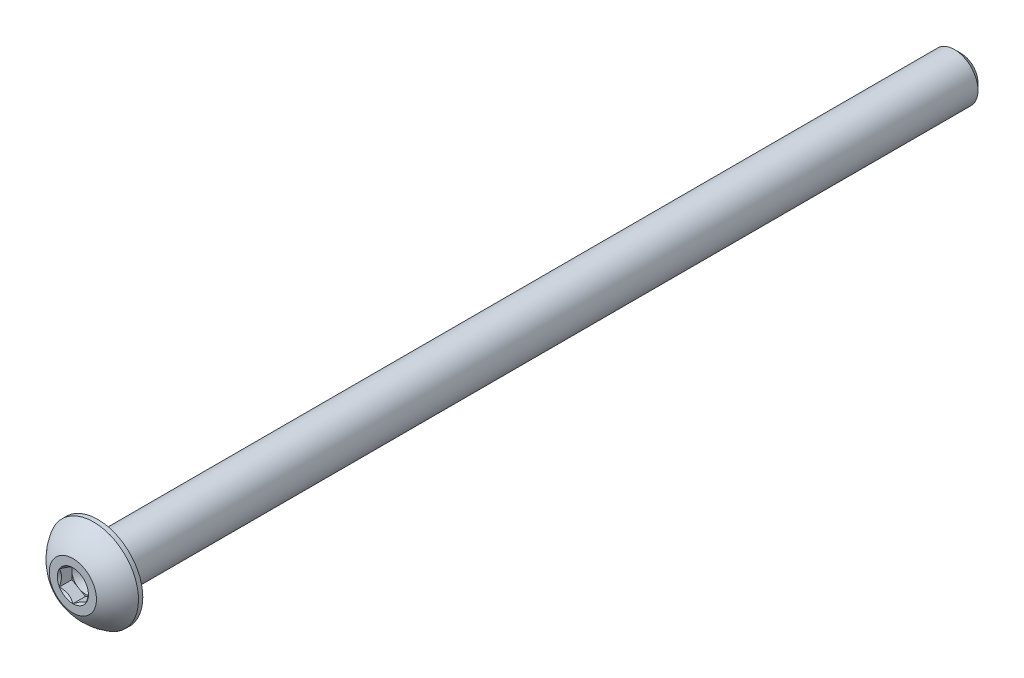
SolidWorks part; units mm, degrees
ref_plane "Front" through (0, 0, 0) normal (0, 0, 1) x (1, 0, 0)
ref_plane "Top" through (0, 0, 0) normal (0, 1, 0) x (1, 0, 0)
ref_plane "Right" through (0, 0, 0) normal (1, 0, 0) x (0, 0, -1)
sketch "Sketch1" plane through (0, 0, 0) normal (1, 0, 0) x (0, 0, -1)
  line L0 (0, 0) -> (-2.2098, 0) construction
  line L1 (0, 0) -> (76.2, 0)
  line L2 (0, 0) -> (0, 2.0828)
  line L3 (0, 2.0828) -> (76.2, 2.0828)
  line L4 (76.2, 0) -> (76.2, 2.0828)
  line L5 (0, -2.0828) -> (76.2, -2.0828) construction
  dimension "D1" = 76.2
  dimension "Thread Dia" = 4.1656
  dimension "Length" = 76.2
  dimension "Head Height" = 2.2098
revolve "Revolve1" add sketch "Sketch1" angle 360 about L0
ref_plane "Plane1" through (0, 0, 2.2098) normal (0, 0, 1) x (1, 0, 0)
chamfer "Chamfer1" distance 0.5953 angle 45 1 edges at (0, 2.0828, -76.2)
sketch "Sketch10" plane through (0, 0, 0) normal (1, 0, 0) x (0, 0, -1)
  line L0 (76.2, 2.0828) -> (76.8945, 2.0828)
  line L1 (76.8945, 2.0828) -> (76.5969, 1.5672)
  line L2 (76.5969, 1.5672) -> (76.4977, 1.5672)
  line L3 (76.4977, 1.5672) -> (76.2, 2.0828)
  line L4 (76.3488, 1.825) -> (76.7457, 1.825) construction
  dimension "D1" = 60
  dimension "D2" = 0.0992
  dimension "D3" = 0.3969
sketch "Sketch11" plane through (0, 0, -76.2) normal (0, 0, -1) x (-1, 0, 0)
  circle A1 centre (0, 0) radius 1.4875
  circle A2 centre (0, 0) radius 1.4875
  dimension "D1" = 0
curve "Helix/Spiral1" [suppressed] pitch 0.7937 height 79.375 turns 100
sweep "Cut-Sweep1" [suppressed] cut profiles "Sketch10" path "Helix/Spiral1"
sketch "Sketch4" plane through (0, 0, 0) normal (0, 0, 1) x (1, 0, 0)
  circle A0 centre (0, 0) radius 3.9624
  dimension "Head Dia" = 7.9248
extrude "Extrude1" add sketch "Sketch4" along normal up to surface (2.2098 mm away) up to plane "Plane1"
sketch "Sketch9" plane through (0, 0, 0) normal (1, 0, 0) x (0, 0, -1)
  line L0 (0, 3.9624) -> (-0.381, 3.9624)
  line L1 (0, 3.9624) -> (0, 4.3434)
  line L2 (0, 4.3434) -> (-2.5908, 4.3434)
  line L3 (0, 0) -> (-2.2098, 0) construction
  line L4 (-2.5908, 4.3434) -> (-2.5908, 2.0828)
  line L5 (-2.5908, 2.0828) -> (-2.2098, 2.0828)
  line L6 (0, 0) -> (0, 2.0828) construction
  line L10 (0, 3.9624) -> (-2.2098, 3.9624) construction
  line L11 (0, 2.0828) -> (76.2, 2.0828) construction
  line L12 (-2.2098, 3.9624) -> (-2.2098, -3.9624) construction
  arc A0 (-2.2098, 2.0828) -> (-0.381, 3.9624) centre (1.8112, 0) cw
  dimension "Side Head Height" = 0.381
revolve "Cut-Revolve3" cut sketch "Sketch9" angle 360 about L3
sketch "Sketch6" plane through (0, 0, 2.2098) normal (0, 0, 1) x (1, 0, 0)
  line L1 (0, -1.3748) -> (1.1906, -0.6874)
  line L2 (1.1906, -0.6874) -> (1.1906, 0.6874)
  line L3 (1.1906, 0.6874) -> (0, 1.3748)
  line L4 (0, 1.3748) -> (-1.1906, 0.6874)
  line L5 (-1.1906, 0.6874) -> (-1.1906, -0.6874)
  line L6 (-1.1906, -0.6874) -> (0, -1.3748)
  circle A0 centre (0, 0) radius 1.1906 construction
  dimension "Hex" = 2.3813
extrude "Cut-Extrude1" cut sketch "Sketch6" against normal blind 1.1049
sketch "Sketch7" plane through (0, 0, 2.2098) normal (0, 0, 1) x (1, 0, 0)
  circle A0 centre (0, 0) radius 1.3748
extrude "Cut-Extrude4" cut sketch "Sketch7" against normal blind 1.1049 draft 45
sketch "Sketch8" plane through (0, 0, 1.1049) normal (0, 0, 1) x (1, 0, 0)
  circle A0 centre (0, 0) radius 1.1906 construction
  circle A1 centre (0, 0) radius 1.1906
extrude "Cut-Extrude5" cut sketch "Sketch8" against normal blind 0.3683 draft 60
sketch "Sketch12" [suppressed] plane through (0, 0, 0) normal (1, 0, 0) x (0, 0, -1)
  line L1 (0, -2.0828) -> (76.2, -2.0828) construction
  spline S2 degree 2 poles (75.6047, 0.019) (75.5523, 0.8706) (75.5055, 1.4728) (75.4393, 2.3231) (75.3732, 2.0118) (75.307, 1.7006) (75.2409, 0.5391) (75.1747, -0.6225) (75.1086, -1.4728) (75.0424, -2.3231) (74.9763, -2.0118) (74.9102, -1.7006) (74.844, -0.5391) (74.7779, 0.6225) (74.7117, 1.4728) (74.6456, 2.3231) (74.5794, 2.0118) (74.5133, 1.7006) (74.4471, 0.5391) (74.381, -0.6225) (74.3148, -1.4728) (74.2487, -2.3231) (74.1826, -2.0118) (74.1164, -1.7006) (74.0503, -0.5391) (73.9841, 0.6225) (73.918, 1.4728) (73.8518, 2.3231) (73.7857, 2.0118) (73.7195, 1.7006) (73.6534, 0.5391) (73.5872, -0.6225) (73.5211, -1.4728) (73.4549, -2.3231) (73.3888, -2.0118) (73.3227, -1.7006) (73.2565, -0.5391) (73.1904, 0.6225) (73.1242, 1.4728) (73.0581, 2.3231) (72.9919, 2.0118) (72.9258, 1.7006) (72.8596, 0.5391) (72.7935, -0.6225) (72.7273, -1.4728) (72.6612, -2.3231) (72.5951, -2.0118) (72.5289, -1.7006) (72.4628, -0.5391) (72.3966, 0.6225) (72.3305, 1.4728) (72.2643, 2.3231) (72.1982, 2.0118) (72.132, 1.7006) (72.0659, 0.5391) (71.9997, -0.6225) (71.9336, -1.4728) (71.8674, -2.3231) (71.8013, -2.0118) (71.7352, -1.7006) (71.669, -0.5391) (71.6029, 0.6225) (71.5367, 1.4728) (71.4706, 2.3231) (71.4044, 2.0118) (71.3383, 1.7006) (71.2721, 0.5391) (71.206, -0.6225) (71.1398, -1.4728) (71.0737, -2.3231) (71.0076, -2.0118) (70.9414, -1.7006) (70.8753, -0.5391) (70.8091, 0.6225) (70.743, 1.4728) (70.6768, 2.3231) (70.6107, 2.0118) (70.5445, 1.7006) (70.4784, 0.5391) (70.4122, -0.6225) (70.3461, -1.4728) (70.2799, -2.3231) (70.2138, -2.0118) (70.1477, -1.7006) (70.0815, -0.5391) (70.0154, 0.6225) (69.9492, 1.4728) (69.8831, 2.3231) (69.8169, 2.0118) (69.7508, 1.7006) (69.6846, 0.5391) (69.6185, -0.6225) (69.5523, -1.4728) (69.4862, -2.3231) (69.4201, -2.0118) (69.3539, -1.7006) (69.2878, -0.5391) (69.2216, 0.6225) (69.1555, 1.4728) (69.0893, 2.3231) (69.0232, 2.0118) (68.957, 1.7006) (68.8909, 0.5391) (68.8247, -0.6225) (68.7586, -1.4728) (68.6924, -2.3231) (68.6263, -2.0118) (68.5602, -1.7006) (68.494, -0.5391) (68.4279, 0.6225) (68.3617, 1.4728) (68.2956, 2.3231) (68.2294, 2.0118) (68.1633, 1.7006) (68.0971, 0.5391) (68.031, -0.6225) (67.9648, -1.4728) (67.8987, -2.3231) (67.8326, -2.0118) (67.7664, -1.7006) (67.7003, -0.5391) (67.6341, 0.6225) (67.568, 1.4728) (67.5018, 2.3231) (67.4357, 2.0118) (67.3695, 1.7006) (67.3034, 0.5391) (67.2372, -0.6225) (67.1711, -1.4728) (67.1049, -2.3231) (67.0388, -2.0118) (66.9727, -1.7006) (66.9065, -0.5391) (66.8404, 0.6225) (66.7742, 1.4728) (66.7081, 2.3231) (66.6419, 2.0118) (66.5758, 1.7006) (66.5096, 0.5391) (66.4435, -0.6225) (66.3773, -1.4728) (66.3112, -2.3231) (66.2451, -2.0118) (66.1789, -1.7006) (66.1128, -0.5391) (66.0466, 0.6225) (65.9805, 1.4728) (65.9143, 2.3231) (65.8482, 2.0118) (65.782, 1.7006) (65.7159, 0.5391) (65.6497, -0.6225) (65.5836, -1.4728) (65.5174, -2.3231) (65.4513, -2.0118) (65.3852, -1.7006) (65.319, -0.5391) (65.2529, 0.6225) (65.1867, 1.4728) (65.1206, 2.3231) (65.0544, 2.0118) (64.9883, 1.7006) (64.9221, 0.5391) (64.856, -0.6225) (64.7898, -1.4728) (64.7237, -2.3231) (64.6576, -2.0118) (64.5914, -1.7006) (64.5253, -0.5391) (64.4591, 0.6225) (64.393, 1.4728) (64.3268, 2.3231) (64.2607, 2.0118) (64.1945, 1.7006) (64.1284, 0.5391) (64.0622, -0.6225) (63.9961, -1.4728) (63.9299, -2.3231) (63.8638, -2.0118) (63.7977, -1.7006) (63.7315, -0.5391) (63.6654, 0.6225) (63.5992, 1.4728) (63.5331, 2.3231) (63.4669, 2.0118) (63.4008, 1.7006) (63.3346, 0.5391) (63.2685, -0.6225) (63.2023, -1.4728) (63.1362, -2.3231) (63.0701, -2.0118) (63.0039, -1.7006) (62.9378, -0.5391) (62.8716, 0.6225) (62.8055, 1.4728) (62.7393, 2.3231) (62.6732, 2.0118) (62.607, 1.7006) (62.5409, 0.5391) (62.4747, -0.6225) (62.4086, -1.4728) (62.3424, -2.3231) (62.2763, -2.0118) (62.2102, -1.7006) (62.144, -0.5391) (62.0779, 0.6225) (62.0117, 1.4728) (61.9456, 2.3231) (61.8794, 2.0118) (61.8133, 1.7006) (61.7471, 0.5391) (61.681, -0.6225) (61.6148, -1.4728) (61.5487, -2.3231) (61.4826, -2.0118) (61.4164, -1.7006) (61.3503, -0.5391) (61.2841, 0.6225) (61.218, 1.4728) (61.1518, 2.3231) (61.0857, 2.0118) (61.0195, 1.7006) (60.9534, 0.5391) (60.8872, -0.6225) (60.8211, -1.4728) (60.7549, -2.3231) (60.6888, -2.0118) (60.6227, -1.7006) (60.5565, -0.5391) (60.4904, 0.6225) (60.4242, 1.4728) (60.3581, 2.3231) (60.2919, 2.0118) (60.2258, 1.7006) (60.1596, 0.5391) (60.0935, -0.6225) (60.0273, -1.4728) (59.9612, -2.3231) (59.8951, -2.0118) (59.8289, -1.7006) (59.7628, -0.5391) (59.6966, 0.6225) (59.6305, 1.4728) (59.5643, 2.3231) (59.4982, 2.0118) (59.432, 1.7006) (59.3659, 0.5391) (59.2997, -0.6225) (59.2336, -1.4728) (59.1674, -2.3231) (59.1013, -2.0118) (59.0352, -1.7006) (58.969, -0.5391) (58.9029, 0.6225) (58.8367, 1.4728) (58.7706, 2.3231) (58.7044, 2.0118) (58.6383, 1.7006) (58.5721, 0.5391) (58.506, -0.6225) (58.4398, -1.4728) (58.3737, -2.3231) (58.3076, -2.0118) (58.2414, -1.7006) (58.1753, -0.5391) (58.1091, 0.6225) (58.043, 1.4728) (57.9768, 2.3231) (57.9107, 2.0118) (57.8445, 1.7006) (57.7784, 0.5391) (57.7122, -0.6225) (57.6461, -1.4728) (57.5799, -2.3231) (57.5138, -2.0118) (57.4477, -1.7006) (57.3815, -0.5391) (57.3154, 0.6225) (57.2492, 1.4728) (57.1831, 2.3231) (57.1169, 2.0118) (57.0508, 1.7006) (56.9846, 0.5391) (56.9185, -0.6225) (56.8523, -1.4728) (56.7862, -2.3231) (56.7201, -2.0118) (56.6539, -1.7006) (56.5878, -0.5391) (56.5216, 0.6225) (56.4555, 1.4728) (56.3893, 2.3231) (56.3232, 2.0118) (56.257, 1.7006) (56.1909, 0.5391) (56.1247, -0.6225) (56.0586, -1.4728) (55.9924, -2.3231) (55.9263, -2.0118) (55.8602, -1.7006) (55.794, -0.5391) (55.7279, 0.6225) (55.6617, 1.4728) (55.5956, 2.3231) (55.5294, 2.0118) (55.4633, 1.7006) (55.3971, 0.5391) (55.331, -0.6225) (55.2648, -1.4728) (55.1987, -2.3231) (55.1326, -2.0118) (55.0664, -1.7006) (55.0003, -0.5391) (54.9341, 0.6225) (54.868, 1.4728) (54.8018, 2.3231) (54.7357, 2.0118) (54.6695, 1.7006) (54.6034, 0.5391) (54.5372, -0.6225) (54.4711, -1.4728) (54.4049, -2.3231) (54.3388, -2.0118) (54.2727, -1.7006) (54.2065, -0.5391) (54.1404, 0.6225) (54.0742, 1.4728) (54.0081, 2.3231) (53.9419, 2.0118) (53.8758, 1.7006) (53.8096, 0.5391) (53.7435, -0.6225) (53.6773, -1.4728) (53.6112, -2.3231) (53.5451, -2.0118) (53.4789, -1.7006) (53.4128, -0.5391) (53.3466, 0.6225) (53.2805, 1.4728) (53.2143, 2.3231) (53.1482, 2.0118) (53.082, 1.7006) (53.0159, 0.5391) (52.9497, -0.6225) (52.8836, -1.4728) (52.8174, -2.3231) (52.7513, -2.0118) (52.6852, -1.7006) (52.619, -0.5391) (52.5529, 0.6225) (52.4867, 1.4728) (52.4206, 2.3231) (52.3544, 2.0118) (52.2883, 1.7006) (52.2221, 0.5391) (52.156, -0.6225) (52.0898, -1.4728) (52.0237, -2.3231) (51.9576, -2.0118) (51.8914, -1.7006) (51.8253, -0.5391) (51.7591, 0.6225) (51.693, 1.4728) (51.6268, 2.3231) (51.5607, 2.0118) (51.4945, 1.7006) (51.4284, 0.5391) (51.3622, -0.6225) (51.2961, -1.4728) (51.2299, -2.3231) (51.1638, -2.0118) (51.0977, -1.7006) (51.0315, -0.5391) (50.9654, 0.6225) (50.8992, 1.4728) (50.8331, 2.3231) (50.7669, 2.0118) (50.7008, 1.7006) (50.6346, 0.5391) (50.5685, -0.6225) (50.5023, -1.4728) (50.4362, -2.3231) (50.3701, -2.0118) (50.3039, -1.7006) (50.2378, -0.5391) (50.1716, 0.6225) (50.1055, 1.4728) (50.0393, 2.3231) (49.9732, 2.0118) (49.907, 1.7006) (49.8409, 0.5391) (49.7747, -0.6225) (49.7086, -1.4728) (49.6424, -2.3231) (49.5763, -2.0118) (49.5102, -1.7006) (49.444, -0.5391) (49.3779, 0.6225) (49.3117, 1.4728) (49.2456, 2.3231) (49.1794, 2.0118) (49.1133, 1.7006) (49.0471, 0.5391) (48.981, -0.6225) (48.9148, -1.4728) (48.8487, -2.3231) (48.7826, -2.0118) (48.7164, -1.7006) (48.6503, -0.5391) (48.5841, 0.6225) (48.518, 1.4728) (48.4518, 2.3231) (48.3857, 2.0118) (48.3195, 1.7006) (48.2534, 0.5391) (48.1872, -0.6225) (48.1211, -1.4728) (48.0549, -2.3231) (47.9888, -2.0118) (47.9227, -1.7006) (47.8565, -0.5391) (47.7904, 0.6225) (47.7242, 1.4728) (47.6581, 2.3231) (47.5919, 2.0118) (47.5258, 1.7006) (47.4596, 0.5391) (47.3935, -0.6225) (47.3273, -1.4728) (47.2612, -2.3231) (47.1951, -2.0118) (47.1289, -1.7006) (47.0628, -0.5391) (46.9966, 0.6225) (46.9305, 1.4728) (46.8643, 2.3231) (46.7982, 2.0118) (46.732, 1.7006) (46.6659, 0.5391) (46.5997, -0.6225) (46.5336, -1.4728) (46.4674, -2.3231) (46.4013, -2.0118) (46.3352, -1.7006) (46.269, -0.5391) (46.2029, 0.6225) (46.1367, 1.4728) (46.0706, 2.3231) (46.0044, 2.0118) (45.9383, 1.7006) (45.8721, 0.5391) (45.806, -0.6225) (45.7398, -1.4728) (45.6737, -2.3231) (45.6076, -2.0118) (45.5414, -1.7006) (45.4753, -0.5391) (45.4091, 0.6225) (45.343, 1.4728) (45.2768, 2.3231) (45.2107, 2.0118) (45.1445, 1.7006) (45.0784, 0.5391) (45.0122, -0.6225) (44.9461, -1.4728) (44.8799, -2.3231) (44.8138, -2.0118) (44.7477, -1.7006) (44.6815, -0.5391) (44.6154, 0.6225) (44.5492, 1.4728) (44.4831, 2.3231) (44.4169, 2.0118) (44.3508, 1.7006) (44.2846, 0.5391) (44.2185, -0.6225) (44.1523, -1.4728) (44.0862, -2.3231) (44.0201, -2.0118) (43.9539, -1.7006) (43.8878, -0.5391) (43.8216, 0.6225) (43.7555, 1.4728) (43.6893, 2.3231) (43.6232, 2.0118) (43.557, 1.7006) (43.4909, 0.5391) (43.4247, -0.6225) (43.3586, -1.4728) (43.2924, -2.3231) (43.2263, -2.0118) (43.1602, -1.7006) (43.094, -0.5391) (43.0279, 0.6225) (42.9617, 1.4728) (42.8956, 2.3231) (42.8294, 2.0118) (42.7633, 1.7006) (42.6971, 0.5391) (42.631, -0.6225) (42.5648, -1.4728) (42.4987, -2.3231) (42.4326, -2.0118) (42.3664, -1.7006) (42.3003, -0.5391) (42.2341, 0.6225) (42.168, 1.4728) (42.1018, 2.3231) (42.0357, 2.0118) (41.9695, 1.7006) (41.9034, 0.5391) (41.8372, -0.6225) (41.7711, -1.4728) (41.7049, -2.3231) (41.6388, -2.0118) (41.5727, -1.7006) (41.5065, -0.5391) (41.4404, 0.6225) (41.3742, 1.4728) (41.3081, 2.3231) (41.2419, 2.0118) (41.1758, 1.7006) (41.1096, 0.5391) (41.0435, -0.6225) (40.9773, -1.4728) (40.9112, -2.3231) (40.8451, -2.0118) (40.7789, -1.7006) (40.7128, -0.5391) (40.6466, 0.6225) (40.5805, 1.4728) (40.5143, 2.3231) (40.4482, 2.0118) (40.382, 1.7006) (40.3159, 0.5391) (40.2497, -0.6225) (40.1836, -1.4728) (40.1174, -2.3231) (40.0513, -2.0118) (39.9852, -1.7006) (39.919, -0.5391) (39.8529, 0.6225) (39.7867, 1.4728) (39.7206, 2.3231) (39.6544, 2.0118) (39.5883, 1.7006) (39.5221, 0.5391) (39.456, -0.6225) (39.3898, -1.4728) (39.3237, -2.3231) (39.2576, -2.0118) (39.1914, -1.7006) (39.1253, -0.5391) (39.0591, 0.6225) (38.993, 1.4728) (38.9268, 2.3231) (38.8607, 2.0118) (38.7945, 1.7006) (38.7284, 0.5391) (38.6622, -0.6225) (38.5961, -1.4728) (38.5299, -2.3231) (38.4638, -2.0118) (38.3977, -1.7006) (38.3315, -0.5391) (38.2654, 0.6225) (38.1992, 1.4728) (38.1331, 2.3231) (38.0669, 2.0118) (38.0008, 1.7006) (37.9346, 0.5391) (37.8685, -0.6225) (37.8023, -1.4728) (37.7362, -2.3231) (37.6701, -2.0118) (37.6039, -1.7006) (37.5378, -0.5391) (37.4716, 0.6225) (37.4055, 1.4728) (37.3393, 2.3231) (37.2732, 2.0118) (37.207, 1.7006) (37.1409, 0.5391) (37.0747, -0.6225) (37.0086, -1.4728) (36.9424, -2.3231) (36.8763, -2.0118) (36.8102, -1.7006) (36.744, -0.5391) (36.6779, 0.6225) (36.6117, 1.4728) (36.5456, 2.3231) (36.4794, 2.0118) (36.4133, 1.7006) (36.3471, 0.5391) (36.281, -0.6225) (36.2148, -1.4728) (36.1487, -2.3231) (36.0826, -2.0118) (36.0164, -1.7006) (35.9503, -0.5391) (35.8841, 0.6225) (35.818, 1.4728) (35.7518, 2.3231) (35.6857, 2.0118) (35.6195, 1.7006) (35.5534, 0.5391) (35.4872, -0.6225) (35.4211, -1.4728) (35.3549, -2.3231) (35.2888, -2.0118) (35.2227, -1.7006) (35.1565, -0.5391) (35.0904, 0.6225) (35.0242, 1.4728) (34.9581, 2.3231) (34.8919, 2.0118) (34.8258, 1.7006) (34.7596, 0.5391) (34.6935, -0.6225) (34.6273, -1.4728) (34.5612, -2.3231) (34.4951, -2.0118) (34.4289, -1.7006) (34.3628, -0.5391) (34.2966, 0.6225) (34.2305, 1.4728) (34.1643, 2.3231) (34.0982, 2.0118) (34.032, 1.7006) (33.9659, 0.5391) (33.8997, -0.6225) (33.8336, -1.4728) (33.7674, -2.3231) (33.7013, -2.0118) (33.6352, -1.7006) (33.569, -0.5391) (33.5029, 0.6225) (33.4367, 1.4728) (33.3706, 2.3231) (33.3044, 2.0118) (33.2383, 1.7006) (33.1721, 0.5391) (33.106, -0.6225) (33.0398, -1.4728) (32.9737, -2.3231) (32.9076, -2.0118) (32.8414, -1.7006) (32.7753, -0.5391) (32.7091, 0.6225) (32.643, 1.4728) (32.5768, 2.3231) (32.5107, 2.0118) (32.4445, 1.7006) (32.3784, 0.5391) (32.3122, -0.6225) (32.2461, -1.4728) (32.1799, -2.3231) (32.1138, -2.0118) (32.0477, -1.7006) (31.9815, -0.5391) (31.9154, 0.6225) (31.8492, 1.4728) (31.7831, 2.3231) (31.7169, 2.0118) (31.6508, 1.7006) (31.5846, 0.5391) (31.5185, -0.6225) (31.4523, -1.4728) (31.3862, -2.3231) (31.3201, -2.0118) (31.2539, -1.7006) (31.1878, -0.5391) (31.1216, 0.6225) (31.0555, 1.4728) (30.9893, 2.3231) (30.9232, 2.0118) (30.857, 1.7006) (30.7909, 0.5391) (30.7247, -0.6225) (30.6586, -1.4728) (30.5924, -2.3231) (30.5263, -2.0118) (30.4602, -1.7006) (30.394, -0.5391) (30.3279, 0.6225) (30.2617, 1.4728) (30.1956, 2.3231) (30.1294, 2.0118) (30.0633, 1.7006) (29.9971, 0.5391) (29.931, -0.6225) (29.8648, -1.4728) (29.7987, -2.3231) (29.7326, -2.0118) (29.6664, -1.7006) (29.6003, -0.5391) (29.5341, 0.6225) (29.468, 1.4728) (29.4018, 2.3231) (29.3357, 2.0118) (29.2695, 1.7006) (29.2034, 0.5391) (29.1372, -0.6225) (29.0711, -1.4728) (29.0049, -2.3231) (28.9388, -2.0118) (28.8727, -1.7006) (28.8065, -0.5391) (28.7404, 0.6225) (28.6742, 1.4728) (28.6081, 2.3231) (28.5419, 2.0118) (28.4758, 1.7006) (28.4096, 0.5391) (28.3435, -0.6225) (28.2773, -1.4728) (28.2112, -2.3231) (28.1451, -2.0118) (28.0789, -1.7006) (28.0128, -0.5391) (27.9466, 0.6225) (27.8805, 1.4728) (27.8143, 2.3231) (27.7482, 2.0118) (27.682, 1.7006) (27.6159, 0.5391) (27.5497, -0.6225) (27.4836, -1.4728) (27.4174, -2.3231) (27.3513, -2.0118) (27.2852, -1.7006) (27.219, -0.5391) (27.1529, 0.6225) (27.0867, 1.4728) (27.0206, 2.3231) (26.9544, 2.0118) (26.8883, 1.7006) (26.8221, 0.5391) (26.756, -0.6225) (26.6898, -1.4728) (26.6237, -2.3231) (26.5576, -2.0118) (26.4914, -1.7006) (26.4253, -0.5391) (26.3591, 0.6225) (26.293, 1.4728) (26.2268, 2.3231) (26.1607, 2.0118) (26.0945, 1.7006) (26.0284, 0.5391) (25.9622, -0.6225) (25.8961, -1.4728) (25.8299, -2.3231) (25.7638, -2.0118) (25.6977, -1.7006) (25.6315, -0.5391) (25.5654, 0.6225) (25.4992, 1.4728) (25.4331, 2.3231) (25.3669, 2.0118) (25.3008, 1.7006) (25.2346, 0.5391) (25.1685, -0.6225) (25.1023, -1.4728) (25.0362, -2.3231) (24.9701, -2.0118) (24.9039, -1.7006) (24.8378, -0.5391) (24.7716, 0.6225) (24.7055, 1.4728) (24.6393, 2.3231) (24.5732, 2.0118) (24.507, 1.7006) (24.4409, 0.5391) (24.3747, -0.6225) (24.3086, -1.4728) (24.2424, -2.3231) (24.1763, -2.0118) (24.1102, -1.7006) (24.044, -0.5391) (23.9779, 0.6225) (23.9117, 1.4728) (23.8456, 2.3231) (23.7794, 2.0118) (23.7133, 1.7006) (23.6471, 0.5391) (23.581, -0.6225) (23.5148, -1.4728) (23.4487, -2.3231) (23.3826, -2.0118) (23.3164, -1.7006) (23.2503, -0.5391) (23.1841, 0.6225) (23.118, 1.4728) (23.0518, 2.3231) (22.9857, 2.0118) (22.9195, 1.7006) (22.8534, 0.5391) (22.7872, -0.6225) (22.7211, -1.4728) (22.6549, -2.3231) (22.5888, -2.0118) (22.5227, -1.7006) (22.4565, -0.5391) (22.3904, 0.6225) (22.3242, 1.4728) (22.2581, 2.3231) (22.1919, 2.0118) (22.1258, 1.7006) (22.0596, 0.5391) (21.9935, -0.6225) (21.9273, -1.4728) (21.8612, -2.3231) (21.7951, -2.0118) (21.7289, -1.7006) (21.6628, -0.5391) (21.5966, 0.6225) (21.5305, 1.4728) (21.4643, 2.3231) (21.3982, 2.0118) (21.332, 1.7006) (21.2659, 0.5391) (21.1997, -0.6225) (21.1336, -1.4728) (21.0674, -2.3231) (21.0013, -2.0118) (20.9352, -1.7006) (20.869, -0.5391) (20.8029, 0.6225) (20.7367, 1.4728) (20.6706, 2.3231) (20.6044, 2.0118) (20.5383, 1.7006) (20.4721, 0.5391) (20.406, -0.6225) (20.3398, -1.4728) (20.2737, -2.3231) (20.2076, -2.0118) (20.1414, -1.7006) (20.0753, -0.5391) (20.0091, 0.6225) (19.943, 1.4728) (19.8768, 2.3231) (19.8107, 2.0118) (19.7445, 1.7006) (19.6784, 0.5391) (19.6122, -0.6225) (19.5461, -1.4728) (19.4799, -2.3231) (19.4138, -2.0118) (19.3477, -1.7006) (19.2815, -0.5391) (19.2154, 0.6225) (19.1492, 1.4728) (19.0831, 2.3231) (19.0169, 2.0118) (18.9508, 1.7006) (18.8846, 0.5391) (18.8185, -0.6225) (18.7523, -1.4728) (18.6862, -2.3231) (18.6201, -2.0118) (18.5539, -1.7006) (18.4878, -0.5391) (18.4216, 0.6225) (18.3555, 1.4728) (18.2893, 2.3231) (18.2232, 2.0118) (18.157, 1.7006) (18.0909, 0.5391) (18.0247, -0.6225) (17.9586, -1.4728) (17.8924, -2.3231) (17.8263, -2.0118) (17.7602, -1.7006) (17.694, -0.5391) (17.6279, 0.6225) (17.5617, 1.4728) (17.4956, 2.3231) (17.4294, 2.0118) (17.3633, 1.7006) (17.2971, 0.5391) (17.231, -0.6225) (17.1648, -1.4728) (17.0987, -2.3231) (17.0326, -2.0118) (16.9664, -1.7006) (16.9003, -0.5391) (16.8341, 0.6225) (16.768, 1.4728) (16.7018, 2.3231) (16.6357, 2.0118) (16.5695, 1.7006) (16.5034, 0.5391) (16.4372, -0.6225) (16.3711, -1.4728) (16.3049, -2.3231) (16.2388, -2.0118) (16.1727, -1.7006) (16.1065, -0.5391) (16.0404, 0.6225) (15.9742, 1.4728) (15.9081, 2.3231) (15.8419, 2.0118) (15.7758, 1.7006) (15.7096, 0.5391) (15.6435, -0.6225) (15.5773, -1.4728) (15.5112, -2.3231) (15.4451, -2.0118) (15.3789, -1.7006) (15.3128, -0.5391) (15.2466, 0.6225) (15.1805, 1.4728) (15.1143, 2.3231) (15.0482, 2.0118) (14.982, 1.7006) (14.9159, 0.5391) (14.8497, -0.6225) (14.7836, -1.4728) (14.7174, -2.3231) (14.6513, -2.0118) (14.5852, -1.7006) (14.519, -0.5391) (14.4529, 0.6225) (14.3867, 1.4728) (14.3206, 2.3231) (14.2544, 2.0118) (14.1883, 1.7006) (14.1221, 0.5391) (14.056, -0.6225) (13.9898, -1.4728) (13.9237, -2.3231) (13.8576, -2.0118) (13.7914, -1.7006) (13.7253, -0.5391) (13.6591, 0.6225) (13.593, 1.4728) (13.5268, 2.3231) (13.4607, 2.0118) (13.3945, 1.7006) (13.3284, 0.5391) (13.2622, -0.6225) (13.1961, -1.4728) (13.1299, -2.3231) (13.0638, -2.0118) (12.9977, -1.7006) (12.9315, -0.5391) (12.8654, 0.6225) (12.7992, 1.4728) (12.7331, 2.3231) (12.6669, 2.0118) (12.6008, 1.7006) (12.5346, 0.5391) (12.4685, -0.6225) (12.4023, -1.4728) (12.3362, -2.3231) (12.2701, -2.0118) (12.2039, -1.7006) (12.1378, -0.5391) (12.0716, 0.6225) (12.0055, 1.4728) (11.9393, 2.3231) (11.8732, 2.0118) (11.807, 1.7006) (11.7409, 0.5391) (11.6747, -0.6225) (11.6086, -1.4728) (11.5424, -2.3231) (11.4763, -2.0118) (11.4102, -1.7006) (11.344, -0.5391) (11.2779, 0.6225) (11.2117, 1.4728) (11.1456, 2.3231) (11.0794, 2.0118) (11.0133, 1.7006) (10.9471, 0.5391) (10.881, -0.6225) (10.8148, -1.4728) (10.7487, -2.3231) (10.6826, -2.0118) (10.6164, -1.7006) (10.5503, -0.5391) (10.4841, 0.6225) (10.418, 1.4728) (10.3518, 2.3231) (10.2857, 2.0118) (10.2195, 1.7006) (10.1534, 0.5391) (10.0872, -0.6225) (10.0211, -1.4728) (9.9549, -2.3231) (9.8888, -2.0118) (9.8227, -1.7006) (9.7565, -0.5391) (9.6904, 0.6225) (9.6242, 1.4728) (9.5581, 2.3231) (9.4919, 2.0118) (9.4258, 1.7006) (9.3596, 0.5391) (9.2935, -0.6225) (9.2273, -1.4728) (9.1612, -2.3231) (9.0951, -2.0118) (9.0289, -1.7006) (8.9628, -0.5391) (8.8966, 0.6225) (8.8305, 1.4728) (8.7643, 2.3231) (8.6982, 2.0118) (8.632, 1.7006) (8.5659, 0.5391) (8.4997, -0.6225) (8.4336, -1.4728) (8.3674, -2.3231) (8.3013, -2.0118) (8.2352, -1.7006) (8.169, -0.5391) (8.1029, 0.6225) (8.0367, 1.4728) (7.9706, 2.3231) (7.9044, 2.0118) (7.8383, 1.7006) (7.7721, 0.5391) (7.706, -0.6225) (7.6398, -1.4728) (7.5737, -2.3231) (7.5076, -2.0118) (7.4414, -1.7006) (7.3753, -0.5391) (7.3091, 0.6225) (7.243, 1.4728) (7.1768, 2.3231) (7.1107, 2.0118) (7.0445, 1.7006) (6.9784, 0.5391) (6.9122, -0.6225) (6.8461, -1.4728) (6.7799, -2.3231) (6.7138, -2.0118) (6.6477, -1.7006) (6.5815, -0.5391) (6.5154, 0.6225) (6.4492, 1.4728) (6.3831, 2.3231) (6.3169, 2.0118) (6.2508, 1.7006) (6.1846, 0.5391) (6.1185, -0.6225) (6.0523, -1.4728) (5.9862, -2.3231) (5.9201, -2.0118) (5.8539, -1.7006) (5.7878, -0.5391) (5.7216, 0.6225) (5.6555, 1.4728) (5.5893, 2.3231) (5.5232, 2.0118) (5.457, 1.7006) (5.3909, 0.5391) (5.3247, -0.6225) (5.2586, -1.4728) (5.1924, -2.3231) (5.1263, -2.0118) (5.0602, -1.7006) (4.994, -0.5391) (4.9279, 0.6225) (4.8617, 1.4728) (4.7956, 2.3231) (4.7294, 2.0118) (4.6633, 1.7006) (4.5971, 0.5391) (4.531, -0.6225) (4.4648, -1.4728) (4.3987, -2.3231) (4.3326, -2.0118) (4.2664, -1.7006) (4.2003, -0.5391) (4.1341, 0.6225) (4.068, 1.4728) (4.0018, 2.3231) (3.9357, 2.0118) (3.8695, 1.7006) (3.8034, 0.5391) (3.7372, -0.6225) (3.6711, -1.4728) (3.6049, -2.3231) (3.5388, -2.0118) (3.4727, -1.7006) (3.4065, -0.5391) (3.3404, 0.6225) (3.2742, 1.4728) (3.2081, 2.3231) (3.1419, 2.0118) (3.0758, 1.7006) (3.0096, 0.5391) (2.9435, -0.6225) (2.8773, -1.4728) (2.8112, -2.3231) (2.7451, -2.0118) (2.6789, -1.7006) (2.6128, -0.5391) (2.5466, 0.6225) (2.4805, 1.4728) (2.4143, 2.3231) (2.3482, 2.0118) (2.282, 1.7006) (2.2159, 0.5391) (2.1497, -0.6225) (2.0836, -1.4728) (2.0174, -2.3231) (1.9513, -2.0118) (1.8852, -1.7006) (1.819, -0.5391) (1.7529, 0.6225) (1.6867, 1.4728) (1.6206, 2.3231) (1.5544, 2.0118) (1.4883, 1.7006) (1.4221, 0.5391) (1.356, -0.6225) (1.2898, -1.4728) (1.2237, -2.3231) (1.1576, -2.0118) (1.0914, -1.7006) (1.0253, -0.5391) (0.9591, 0.6225) (0.893, 1.4728) (0.8268, 2.3231) (0.7607, 2.0118) (0.6945, 1.7006) (0.6284, 0.5391) (0.5622, -0.6225) (0.4961, -1.4728) (0.4299, -2.3231) (0.3638, -2.0118) (0.2977, -1.7006) (0.2315, -0.5391) (0.1654, 0.6225) (0.0992, 1.4728) (0.0524, 2.0749) (0, 2.0827) knots 0.008772 0.008772 0.008772 0.01 0.01 0.011667 0.011667 0.013333 0.013333 0.015 0.015 0.016667 0.016667 0.018333 0.018333 0.02 0.02 0.021667 0.021667 0.023333 0.023333 0.025 0.025 0.026667 0.026667 0.028333 0.028333 0.03 0.03 0.031667 0.031667 0.033333 0.033333 0.035 0.035 0.036667 0.036667 0.038333 0.038333 0.04 0.04 0.041667 0.041667 0.043333 0.043333 0.045 0.045 0.046667 0.046667 0.048333 0.048333 0.05 0.05 0.051667 0.051667 0.053333 0.053333 0.055 0.055 0.056667 0.056667 0.058333 0.058333 0.06 0.06 0.061667 0.061667 0.063333 0.063333 0.065 0.065 0.066667 0.066667 0.068333 0.068333 0.07 0.07 0.071667 0.071667 0.073333 0.073333 0.075 0.075 0.076667 0.076667 0.078333 0.078333 0.08 0.08 0.081667 0.081667 0.083333 0.083333 0.085 0.085 0.086667 0.086667 0.088333 0.088333 0.09 0.09 0.091667 0.091667 0.093333 0.093333 0.095 0.095 0.096667 0.096667 0.098333 0.098333 0.1 0.1 0.101667 0.101667 0.103333 0.103333 0.105 0.105 0.106667 0.106667 0.108333 0.108333 0.11 0.11 0.111667 0.111667 0.113333 0.113333 0.115 0.115 0.116667 0.116667 0.118333 0.118333 0.12 0.12 0.121667 0.121667 0.123333 0.123333 0.125 0.125 0.126667 0.126667 0.128333 0.128333 0.13 0.13 0.131667 0.131667 0.133333 0.133333 0.135 0.135 0.136667 0.136667 0.138333 0.138333 0.14 0.14 0.141667 0.141667 0.143333 0.143333 0.145 0.145 0.146667 0.146667 0.148333 0.148333 0.15 0.15 0.151667 0.151667 0.153333 0.153333 0.155 0.155 0.156667 0.156667 0.158333 0.158333 0.16 0.16 0.161667 0.161667 0.163333 0.163333 0.165 0.165 0.166667 0.166667 0.168333 0.168333 0.17 0.17 0.171667 0.171667 0.173333 0.173333 0.175 0.175 0.176667 0.176667 0.178333 0.178333 0.18 0.18 0.181667 0.181667 0.183333 0.183333 0.185 0.185 0.186667 0.186667 0.188333 0.188333 0.19 0.19 0.191667 0.191667 0.193333 0.193333 0.195 0.195 0.196667 0.196667 0.198333 0.198333 0.2 0.2 0.201667 0.201667 0.203333 0.203333 0.205 0.205 0.206667 0.206667 0.208333 0.208333 0.21 0.21 0.211667 0.211667 0.213333 0.213333 0.215 0.215 0.216667 0.216667 0.218333 0.218333 0.22 0.22 0.221667 0.221667 0.223333 0.223333 0.225 0.225 0.226667 0.226667 0.228333 0.228333 0.23 0.23 0.231667 0.231667 0.233333 0.233333 0.235 0.235 0.236667 0.236667 0.238333 0.238333 0.24 0.24 0.241667 0.241667 0.243333 0.243333 0.245 0.245 0.246667 0.246667 0.248333 0.248333 0.25 0.25 0.251667 0.251667 0.253333 0.253333 0.255 0.255 0.256667 0.256667 0.258333 0.258333 0.26 0.26 0.261667 0.261667 0.263333 0.263333 0.265 0.265 0.266667 0.266667 0.268333 0.268333 0.27 0.27 0.271667 0.271667 0.273333 0.273333 0.275 0.275 0.276667 0.276667 0.278333 0.278333 0.28 0.28 0.281667 0.281667 0.283333 0.283333 0.285 0.285 0.286667 0.286667 0.288333 0.288333 0.29 0.29 0.291667 0.291667 0.293333 0.293333 0.295 0.295 0.296667 0.296667 0.298333 0.298333 0.3 0.3 0.301667 0.301667 0.303333 0.303333 0.305 0.305 0.306667 0.306667 0.308333 0.308333 0.31 0.31 0.311667 0.311667 0.313333 0.313333 0.315 0.315 0.316667 0.316667 0.318333 0.318333 0.32 0.32 0.321667 0.321667 0.323333 0.323333 0.325 0.325 0.326667 0.326667 0.328333 0.328333 0.33 0.33 0.331667 0.331667 0.333333 0.333333 0.335 0.335 0.336667 0.336667 0.338333 0.338333 0.34 0.34 0.341667 0.341667 0.343333 0.343333 0.345 0.345 0.346667 0.346667 0.348333 0.348333 0.35 0.35 0.351667 0.351667 0.353333 0.353333 0.355 0.355 0.356667 0.356667 0.358333 0.358333 0.36 0.36 0.361667 0.361667 0.363333 0.363333 0.365 0.365 0.366667 0.366667 0.368333 0.368333 0.37 0.37 0.371667 0.371667 0.373333 0.373333 0.375 0.375 0.376667 0.376667 0.378333 0.378333 0.38 0.38 0.381667 0.381667 0.383333 0.383333 0.385 0.385 0.386667 0.386667 0.388333 0.388333 0.39 0.39 0.391667 0.391667 0.393333 0.393333 0.395 0.395 0.396667 0.396667 0.398333 0.398333 0.4 0.4 0.401667 0.401667 0.403333 0.403333 0.405 0.405 0.406667 0.406667 0.408333 0.408333 0.41 0.41 0.411667 0.411667 0.413333 0.413333 0.415 0.415 0.416667 0.416667 0.418333 0.418333 0.42 0.42 0.421667 0.421667 0.423333 0.423333 0.425 0.425 0.426667 0.426667 0.428333 0.428333 0.43 0.43 0.431667 0.431667 0.433333 0.433333 0.435 0.435 0.436667 0.436667 0.438333 0.438333 0.44 0.44 0.441667 0.441667 0.443333 0.443333 0.445 0.445 0.446667 0.446667 0.448333 0.448333 0.45 0.45 0.451667 0.451667 0.453333 0.453333 0.455 0.455 0.456667 0.456667 0.458333 0.458333 0.46 0.46 0.461667 0.461667 0.463333 0.463333 0.465 0.465 0.466667 0.466667 0.468333 0.468333 0.47 0.47 0.471667 0.471667 0.473333 0.473333 0.475 0.475 0.476667 0.476667 0.478333 0.478333 0.48 0.48 0.481667 0.481667 0.483333 0.483333 0.485 0.485 0.486667 0.486667 0.488333 0.488333 0.49 0.49 0.491667 0.491667 0.493333 0.493333 0.495 0.495 0.496667 0.496667 0.498333 0.498333 0.5 0.5 0.501667 0.501667 0.503333 0.503333 0.505 0.505 0.506667 0.506667 0.508333 0.508333 0.51 0.51 0.511667 0.511667 0.513333 0.513333 0.515 0.515 0.516667 0.516667 0.518333 0.518333 0.52 0.52 0.521667 0.521667 0.523333 0.523333 0.525 0.525 0.526667 0.526667 0.528333 0.528333 0.53 0.53 0.531667 0.531667 0.533333 0.533333 0.535 0.535 0.536667 0.536667 0.538333 0.538333 0.54 0.54 0.541667 0.541667 0.543333 0.543333 0.545 0.545 0.546667 0.546667 0.548333 0.548333 0.55 0.55 0.551667 0.551667 0.553333 0.553333 0.555 0.555 0.556667 0.556667 0.558333 0.558333 0.56 0.56 0.561667 0.561667 0.563333 0.563333 0.565 0.565 0.566667 0.566667 0.568333 0.568333 0.57 0.57 0.571667 0.571667 0.573333 0.573333 0.575 0.575 0.576667 0.576667 0.578333 0.578333 0.58 0.58 0.581667 0.581667 0.583333 0.583333 0.585 0.585 0.586667 0.586667 0.588333 0.588333 0.59 0.59 0.591667 0.591667 0.593333 0.593333 0.595 0.595 0.596667 0.596667 0.598333 0.598333 0.6 0.6 0.601667 0.601667 0.603333 0.603333 0.605 0.605 0.606667 0.606667 0.608333 0.608333 0.61 0.61 0.611667 0.611667 0.613333 0.613333 0.615 0.615 0.616667 0.616667 0.618333 0.618333 0.62 0.62 0.621667 0.621667 0.623333 0.623333 0.625 0.625 0.626667 0.626667 0.628333 0.628333 0.63 0.63 0.631667 0.631667 0.633333 0.633333 0.635 0.635 0.636667 0.636667 0.638333 0.638333 0.64 0.64 0.641667 0.641667 0.643333 0.643333 0.645 0.645 0.646667 0.646667 0.648333 0.648333 0.65 0.65 0.651667 0.651667 0.653333 0.653333 0.655 0.655 0.656667 0.656667 0.658333 0.658333 0.66 0.66 0.661667 0.661667 0.663333 0.663333 0.665 0.665 0.666667 0.666667 0.668333 0.668333 0.67 0.67 0.671667 0.671667 0.673333 0.673333 0.675 0.675 0.676667 0.676667 0.678333 0.678333 0.68 0.68 0.681667 0.681667 0.683333 0.683333 0.685 0.685 0.686667 0.686667 0.688333 0.688333 0.69 0.69 0.691667 0.691667 0.693333 0.693333 0.695 0.695 0.696667 0.696667 0.698333 0.698333 0.7 0.7 0.701667 0.701667 0.703333 0.703333 0.705 0.705 0.706667 0.706667 0.708333 0.708333 0.71 0.71 0.711667 0.711667 0.713333 0.713333 0.715 0.715 0.716667 0.716667 0.718333 0.718333 0.72 0.72 0.721667 0.721667 0.723333 0.723333 0.725 0.725 0.726667 0.726667 0.728333 0.728333 0.73 0.73 0.731667 0.731667 0.733333 0.733333 0.735 0.735 0.736667 0.736667 0.738333 0.738333 0.74 0.74 0.741667 0.741667 0.743333 0.743333 0.745 0.745 0.746667 0.746667 0.748333 0.748333 0.75 0.75 0.751667 0.751667 0.753333 0.753333 0.755 0.755 0.756667 0.756667 0.758333 0.758333 0.76 0.76 0.761667 0.761667 0.763333 0.763333 0.765 0.765 0.766667 0.766667 0.768333 0.768333 0.77 0.77 0.771667 0.771667 0.773333 0.773333 0.775 0.775 0.776667 0.776667 0.778333 0.778333 0.78 0.78 0.781667 0.781667 0.783333 0.783333 0.785 0.785 0.786667 0.786667 0.788333 0.788333 0.79 0.79 0.791667 0.791667 0.793333 0.793333 0.795 0.795 0.796667 0.796667 0.798333 0.798333 0.8 0.8 0.801667 0.801667 0.803333 0.803333 0.805 0.805 0.806667 0.806667 0.808333 0.808333 0.81 0.81 0.811667 0.811667 0.813333 0.813333 0.815 0.815 0.816667 0.816667 0.818333 0.818333 0.82 0.82 0.821667 0.821667 0.823333 0.823333 0.825 0.825 0.826667 0.826667 0.828333 0.828333 0.83 0.83 0.831667 0.831667 0.833333 0.833333 0.835 0.835 0.836667 0.836667 0.838333 0.838333 0.84 0.84 0.841667 0.841667 0.843333 0.843333 0.845 0.845 0.846667 0.846667 0.848333 0.848333 0.85 0.85 0.851667 0.851667 0.853333 0.853333 0.855 0.855 0.856667 0.856667 0.858333 0.858333 0.86 0.86 0.861667 0.861667 0.863333 0.863333 0.865 0.865 0.866667 0.866667 0.868333 0.868333 0.87 0.87 0.871667 0.871667 0.873333 0.873333 0.875 0.875 0.876667 0.876667 0.878333 0.878333 0.88 0.88 0.881667 0.881667 0.883333 0.883333 0.885 0.885 0.886667 0.886667 0.888333 0.888333 0.89 0.89 0.891667 0.891667 0.893333 0.893333 0.895 0.895 0.896667 0.896667 0.898333 0.898333 0.9 0.9 0.901667 0.901667 0.903333 0.903333 0.905 0.905 0.906667 0.906667 0.908333 0.908333 0.91 0.91 0.911667 0.911667 0.913333 0.913333 0.915 0.915 0.916667 0.916667 0.918333 0.918333 0.92 0.92 0.921667 0.921667 0.923333 0.923333 0.925 0.925 0.926667 0.926667 0.928333 0.928333 0.93 0.93 0.931667 0.931667 0.933333 0.933333 0.935 0.935 0.936667 0.936667 0.938333 0.938333 0.94 0.94 0.941667 0.941667 0.943333 0.943333 0.945 0.945 0.946667 0.946667 0.948333 0.948333 0.95 0.95 0.951667 0.951667 0.953333 0.953333 0.955 0.955 0.956667 0.956667 0.958333 0.958333 0.96 0.96 0.961228 0.961228 0.961228 weights 0.948065 0.901259 1 0.866025 1 0.866025 1 0.866025 1 0.866025 1 0.866025 1 0.866025 1 0.866025 1 0.866025 1 0.866025 1 0.866025 1 0.866025 1 0.866025 1 0.866025 1 0.866025 1 0.866025 1 0.866025 1 0.866025 1 0.866025 1 0.866025 1 0.866025 1 0.866025 1 0.866025 1 0.866025 1 0.866025 1 0.866025 1 0.866025 1 0.866025 1 0.866025 1 0.866025 1 0.866025 1 0.866025 1 0.866025 1 0.866025 1 0.866025 1 0.866025 1 0.866025 1 0.866025 1 0.866025 1 0.866025 1 0.866025 1 0.866025 1 0.866025 1 0.866025 1 0.866025 1 0.866025 1 0.866025 1 0.866025 1 0.866025 1 0.866025 1 0.866025 1 0.866025 1 0.866025 1 0.866025 1 0.866025 1 0.866025 1 0.866025 1 0.866025 1 0.866025 1 0.866025 1 0.866025 1 0.866025 1 0.866025 1 0.866025 1 0.866025 1 0.866025 1 0.866025 1 0.866025 1 0.866025 1 0.866025 1 0.866025 1 0.866025 1 0.866025 1 0.866025 1 0.866025 1 0.866025 1 0.866025 1 0.866025 1 0.866025 1 0.866025 1 0.866025 1 0.866025 1 0.866025 1 0.866025 1 0.866025 1 0.866025 1 0.866025 1 0.866025 1 0.866025 1 0.866025 1 0.866025 1 0.866025 1 0.866025 1 0.866025 1 0.866025 1 0.866025 1 0.866025 1 0.866025 1 0.866025 1 0.866025 1 0.866025 1 0.866025 1 0.866025 1 0.866025 1 0.866025 1 0.866025 1 0.866025 1 0.866025 1 0.866025 1 0.866025 1 0.866025 1 0.866025 1 0.866025 1 0.866025 1 0.866025 1 0.866025 1 0.866025 1 0.866025 1 0.866025 1 0.866025 1 0.866025 1 0.866025 1 0.866025 1 0.866025 1 0.866025 1 0.866025 1 0.866025 1 0.866025 1 0.866025 1 0.866025 1 0.866025 1 0.866025 1 0.866025 1 0.866025 1 0.866025 1 0.866025 1 0.866025 1 0.866025 1 0.866025 1 0.866025 1 0.866025 1 0.866025 1 0.866025 1 0.866025 1 0.866025 1 0.866025 1 0.866025 1 0.866025 1 0.866025 1 0.866025 1 0.866025 1 0.866025 1 0.866025 1 0.866025 1 0.866025 1 0.866025 1 0.866025 1 0.866025 1 0.866025 1 0.866025 1 0.866025 1 0.866025 1 0.866025 1 0.866025 1 0.866025 1 0.866025 1 0.866025 1 0.866025 1 0.866025 1 0.866025 1 0.866025 1 0.866025 1 0.866025 1 0.866025 1 0.866025 1 0.866025 1 0.866025 1 0.866025 1 0.866025 1 0.866025 1 0.866025 1 0.866025 1 0.866025 1 0.866025 1 0.866025 1 0.866025 1 0.866025 1 0.866025 1 0.866025 1 0.866025 1 0.866025 1 0.866025 1 0.866025 1 0.866025 1 0.866025 1 0.866025 1 0.866025 1 0.866025 1 0.866025 1 0.866025 1 0.866025 1 0.866025 1 0.866025 1 0.866025 1 0.866025 1 0.866025 1 0.866025 1 0.866025 1 0.866025 1 0.866025 1 0.866025 1 0.866025 1 0.866025 1 0.866025 1 0.866025 1 0.866025 1 0.866025 1 0.866025 1 0.866025 1 0.866025 1 0.866025 1 0.866025 1 0.866025 1 0.866025 1 0.866025 1 0.866025 1 0.866025 1 0.866025 1 0.866025 1 0.866025 1 0.866025 1 0.866025 1 0.866025 1 0.866025 1 0.866025 1 0.866025 1 0.866025 1 0.866025 1 0.866025 1 0.866025 1 0.866025 1 0.866025 1 0.866025 1 0.866025 1 0.866025 1 0.866025 1 0.866025 1 0.866025 1 0.866025 1 0.866025 1 0.866025 1 0.866025 1 0.866025 1 0.866025 1 0.866025 1 0.866025 1 0.866025 1 0.866025 1 0.866025 1 0.866025 1 0.866025 1 0.866025 1 0.866025 1 0.866025 1 0.866025 1 0.866025 1 0.866025 1 0.866025 1 0.866025 1 0.866025 1 0.866025 1 0.866025 1 0.866025 1 0.866025 1 0.866025 1 0.866025 1 0.866025 1 0.866025 1 0.866025 1 0.866025 1 0.866025 1 0.866025 1 0.866025 1 0.866025 1 0.866025 1 0.866025 1 0.866025 1 0.866025 1 0.866025 1 0.866025 1 0.866025 1 0.866025 1 0.866025 1 0.866025 1 0.866025 1 0.866025 1 0.866025 1 0.866025 1 0.866025 1 0.866025 1 0.866025 1 0.866025 1 0.866025 1 0.866025 1 0.866025 1 0.866025 1 0.866025 1 0.866025 1 0.866025 1 0.866025 1 0.866025 1 0.866025 1 0.866025 1 0.866025 1 0.866025 1 0.866025 1 0.866025 1 0.866025 1 0.866025 1 0.866025 1 0.866025 1 0.866025 1 0.866025 1 0.866025 1 0.866025 1 0.866025 1 0.866025 1 0.866025 1 0.866025 1 0.866025 1 0.866025 1 0.866025 1 0.866025 1 0.866025 1 0.866025 1 0.866025 1 0.866025 1 0.866025 1 0.866025 1 0.866025 1 0.866025 1 0.866025 1 0.866025 1 0.866025 1 0.866025 1 0.866025 1 0.866025 1 0.866025 1 0.866025 1 0.866025 1 0.866025 1 0.866025 1 0.866025 1 0.866025 1 0.866025 1 0.866025 1 0.866025 1 0.866025 1 0.866025 1 0.866025 1 0.866025 1 0.866025 1 0.866025 1 0.866025 1 0.866025 1 0.866025 1 0.866025 1 0.866025 1 0.866025 1 0.866025 1 0.866025 1 0.866025 1 0.866025 1 0.866025 1 0.866025 1 0.866025 1 0.866025 1 0.866025 1 0.866025 1 0.866025 1 0.866025 1 0.866025 1 0.866025 1 0.866025 1 0.866025 1 0.866025 1 0.866025 1 0.866025 1 0.866025 1 0.866025 1 0.866025 1 0.866025 1 0.866025 1 0.866025 1 0.866025 1 0.866025 1 0.866025 1 0.866025 1 0.866025 1 0.866025 1 0.866025 1 0.866025 1 0.866025 1 0.866025 1 0.866025 1 0.866025 1 0.866025 1 0.866025 1 0.866025 1 0.866025 1 0.866025 1 0.866025 1 0.866025 1 0.866025 1 0.866025 1 0.866025 1 0.866025 1 0.866025 1 0.866025 1 0.866025 1 0.866025 1 0.866025 1 0.866025 1 0.866025 1 0.866025 1 0.866025 1 0.866025 1 0.866025 1 0.866025 1 0.866025 1 0.866025 1 0.866025 1 0.866025 1 0.866025 1 0.866025 1 0.866025 1 0.866025 1 0.866025 1 0.866025 1 0.866025 1 0.866025 1 0.866025 1 0.866025 1 0.866025 1 0.866025 1 0.866025 1 0.866025 1 0.866025 1 0.866025 1 0.866025 1 0.866025 1 0.866025 1 0.866025 1 0.866025 1 0.866025 1 0.866025 1 0.866025 1 0.866025 1 0.866025 1 0.866025 1 0.866025 1 0.866025 1 0.866025 1 0.866025 1 0.866025 1 0.866025 1 0.866025 1 0.866025 1 0.866025 1 0.866025 1 0.866025 1 0.866025 1 0.866025 1 0.866025 1 0.866025 1 0.866025 1 0.866025 1 0.866025 1 0.866025 1 0.866025 1 0.866025 1 0.866025 1 0.866025 1 0.866025 1 0.866025 1 0.866025 1 0.866025 1 0.866025 1 0.866025 1 0.866025 1 0.866025 1 0.866025 1 0.866025 1 0.866025 1 0.866025 1 0.866025 1 0.866025 1 0.866025 1 0.866025 1 0.866025 1 0.866025 1 0.866025 1 0.866025 1 0.866025 1 0.866025 1 0.866025 1 0.866025 1 0.866025 1 0.866025 1 0.866025 1 0.866025 1 0.866025 1 0.866025 1 0.866025 1 0.866025 1 0.866025 1 0.866025 1 0.866025 1 0.866025 1 0.866025 1 0.866025 1 0.866025 1 0.866025 1 0.866025 1 0.866025 1 0.866025 1 0.866025 1 0.866025 1 0.866025 1 0.866025 1 0.866025 1 0.866025 1 0.866025 1 0.866025 1 0.866025 1 0.866025 1 0.866025 1 0.866025 1 0.866025 1 0.866025 1 0.866025 1 0.866025 1 0.866025 1 0.866025 1 0.866025 1 0.866025 1 0.866025 1 0.866025 1 0.866025 1 0.866025 1 0.866025 1 0.866025 1 0.866025 1 0.866025 1 0.866025 1 0.866025 1 0.866025 1 0.866025 1 0.866025 1 0.866025 1 0.866025 1 0.866025 1 0.866025 1 0.866025 1 0.866025 1 0.866025 1 0.866025 1 0.866025 1 0.866025 1 0.866025 1 0.866025 1 0.901259 0.948065 construction
  point P0 (69.452, -2.0828)
equation "\"D1@Cut-Extrude1\"=\"Head Height@Sketch1\"/2"
equation "\"D1@Cut-Extrude4\"=\"D1@Cut-Extrude1\""
equation "\"D1@Cut-Extrude5\"=\"D1@Cut-Extrude1\"/3"
equation "\"D3@Helix/Spiral1\" = \"Length@Sketch1\" + .125"
equation "\"D1@Chamfer1\" = \"D4@Helix/Spiral1\" * .75"
equation "\"D2@Sketch10\" = \"D4@Helix/Spiral1\" * .125"
equation "\"D3@Sketch10\" = \"D4@Helix/Spiral1\" * .5"
